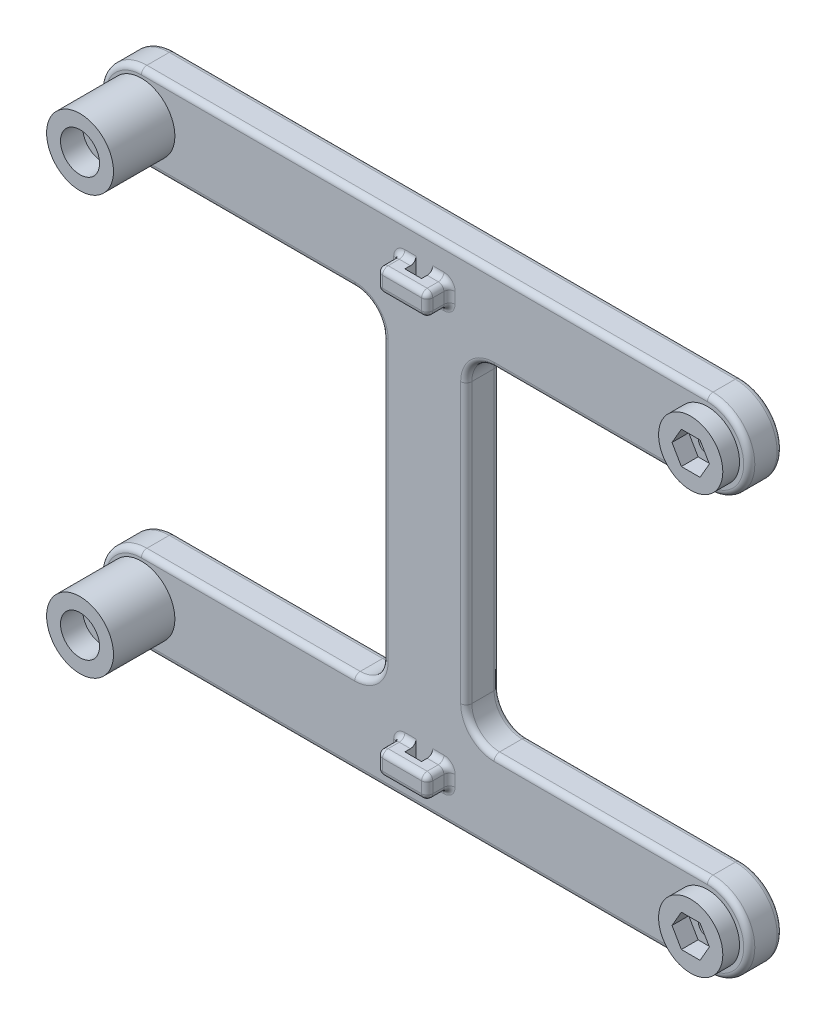
SolidWorks part; units mm, degrees
ref_plane "Front Plane" through (0, 0, 0) normal (0, 0, 1) x (1, 0, 0)
ref_plane "Top Plane" through (0, 0, 0) normal (0, 1, 0) x (1, 0, 0)
ref_plane "Right Plane" through (0, 0, 0) normal (1, 0, 0) x (0, 0, -1)
sketch "Sketch1" plane through (0, 0, 0) normal (0, 0, 1) x (1, 0, 0)
  line L55 (63.25, 7.5) -> (101.5, 7.5)
  line L57 (63.25, 67.5) -> (101.5, 67.5)
  line L97 (0, 82.5) -> (101.5, 82.5)
  line L98 (0, -7.5) -> (101.5, -7.5)
  line L99 (0, 67.5) -> (38.25, 67.5)
  line L100 (0, 7.5) -> (38.25, 7.5)
  line L103 (43.25, 62.5) -> (43.25, 12.5)
  line L105 (58.25, 62.5) -> (58.25, 12.5)
  circle A33 centre (0, 0) radius 4.5
  circle A57 centre (0, 75) radius 4.5
  circle A64 centre (101.5, 75) radius 1.65
  circle A65 centre (101.5, 0) radius 1.65
  arc A66 (0, 82.5) -> (0, 67.5) centre (0, 75) ccw
  arc A67 (0, 7.5) -> (0, -7.5) centre (0, 0) ccw
  arc A68 (101.5, 67.5) -> (101.5, 82.5) centre (101.5, 75) ccw
  arc A69 (101.5, -7.5) -> (101.5, 7.5) centre (101.5, 0) ccw
  arc A70 (58.25, 62.5) -> (63.25, 67.5) centre (63.25, 62.5) cw
  arc A71 (43.25, 62.5) -> (38.25, 67.5) centre (38.25, 62.5) ccw
  arc A72 (58.25, 12.5) -> (63.25, 7.5) centre (63.25, 12.5) ccw
  arc A73 (43.25, 12.5) -> (38.25, 7.5) centre (38.25, 12.5) cw
  point P8 (58.25, 67.5)
  point P25 (58.25, 7.5)
extrude "Boss-Extrude1" add sketch "Sketch1" along normal blind 6
sketch "Sketch2" plane through (0, 0, 6) normal (0, 0, 1) x (1, 0, 0)
  circle A0 centre (0, 75) radius 6
  circle A1 centre (0, 75) radius 3.5
  circle A2 centre (0, 0) radius 3.5
  circle A3 centre (0, 0) radius 6
extrude "Boss-Extrude2" add sketch "Sketch2" along normal blind 12 from offset 1 offset against normal yes
sketch "Sketch3" plane through (0, 0, 0) normal (0, 0, -1) x (-1, 0, 0)
  circle A0 centre (0, 75) radius 3.5
  circle A1 centre (0, 75) radius 1.65
  circle A2 centre (0, 0) radius 3.5
  circle A3 centre (0, 0) radius 1.65
extrude "Boss-Extrude3" add sketch "Sketch3" against normal offset from surface (8 mm away) 4 from offset 5 up to face at (6, 75, 17) offset against normal yes
sketch "Sketch4" plane through (0, 0, 6) normal (0, 0, 1) x (1, 0, 0)
  line L41 (104.8486, 75) -> (103.1743, 77.9)
  line L42 (103.1743, 77.9) -> (99.8257, 77.9)
  line L43 (99.8257, 77.9) -> (98.1514, 75)
  line L44 (98.1514, 75) -> (99.8257, 72.1)
  line L45 (99.8257, 72.1) -> (103.1743, 72.1)
  line L46 (103.1743, 72.1) -> (104.8486, 75)
  line L47 (104.8486, 0) -> (103.1743, 2.9)
  line L48 (103.1743, 2.9) -> (99.8257, 2.9)
  line L49 (99.8257, 2.9) -> (98.1514, 0)
  line L50 (98.1514, 0) -> (99.8257, -2.9)
  line L51 (99.8257, -2.9) -> (103.1743, -2.9)
  line L52 (103.1743, -2.9) -> (104.8486, 0)
  circle A6 centre (101.5, 0) radius 5.76
  circle A7 centre (101.5, 75) radius 5.76
extrude "Boss-Extrude4" add sketch "Sketch4" along normal blind 3
sketch "Sketch5" plane through (0, 0, 0) normal (0, 1, 0) x (1, 0, 0)
  line L0 (49.25, -6) -> (46.25, -6)
  line L1 (55.25, -6) -> (55.25, -10)
  line L2 (55.25, -6) -> (52.25, -6)
  line L3 (46.25, -6) -> (46.25, -10)
  line L4 (55.25, -10) -> (46.25, -10)
  line L5 (52.25, -6) -> (52.25, -8)
  line L6 (49.25, -6) -> (49.25, -8)
  line L7 (52.25, -8) -> (49.25, -8)
extrude "Boss-Extrude5" add sketch "Sketch5" along normal mid plane 4
extrude "Boss-Extrude6" add sketch "Sketch5<2>" along normal mid plane 4 from offset 75
sketch "Sketch5<2>" plane through (0, 0, 0) normal (0, 1, 0) x (1, 0, 0) same geometry as "Sketch5"
fillet "Fillet2" radius 1 60 edges at (53.75, 77, 6) (53.75, 73, 6) (47.75, 73, 6) (47.75, 77, 6) (47.75, 2, 6) (47.75, -2, 6) (53.75, 2, 6) (53.75, -2, 6) (55.25, 75, 6) (55.25, 73, 8) (46.25, 75, 10) (50.75, 77, 10) (50.75, 73, 10) (55.25, 75, 10) (55.25, 77, 8) (46.25, 73, 8) (46.25, 77, 8) (46.25, 75, 6) (46.25, 0, 6) (46.25, 2, 8) (46.25, -2, 8) (55.25, 0, 6) (55.25, 2, 8) (46.25, 0, 10) (50.75, 2, 10) (55.25, -2, 8) (50.75, -2, 10) (55.25, 0, 10) (59.7145, 8.9645, 0) (82.375, 7.5, 0) (109, 0, 0) (50.75, -7.5, 0) (-7.5, 0, 0) (19.125, 7.5, 0) (41.7855, 8.9645, 0) (43.25, 37.5, 0) (41.7855, 66.0355, 0) (19.125, 67.5, 0) (-7.5, 75, 0) (50.75, 82.5, 0) (109, 75, 0) (82.375, 67.5, 0) (59.7145, 66.0355, 0) (59.7145, 8.9645, 6) (82.375, 7.5, 6) (109, 0, 6) (50.75, -7.5, 6) (-7.5, 0, 6) (19.125, 7.5, 6) (41.7855, 8.9645, 6) (43.25, 37.5, 6) (41.7855, 66.0355, 6) (19.125, 67.5, 6) (-7.5, 75, 6) (50.75, 82.5, 6) (109, 75, 6) (82.375, 67.5, 6) (59.7145, 66.0355, 6) (58.25, 37.5, 0) (58.25, 37.5, 6)
